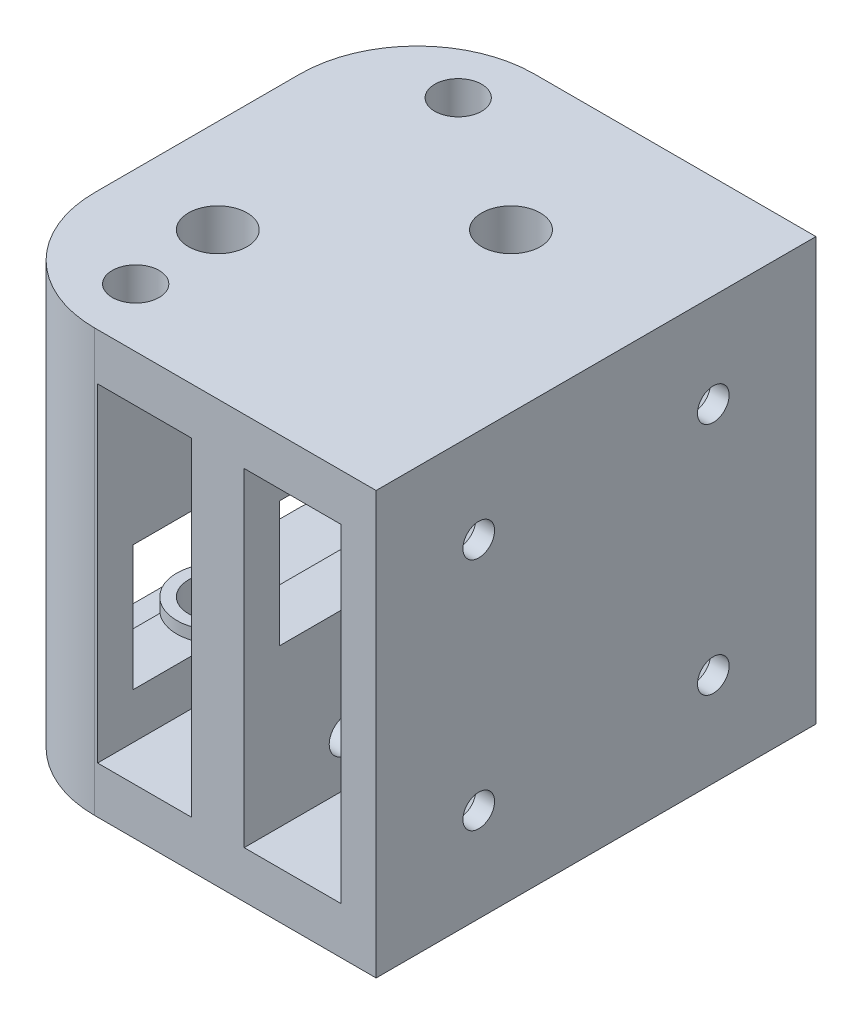
SolidWorks part; units mm, degrees
ref_plane "Front Plane" through (0, 0, 0) normal (0, 0, 1) x (1, 0, 0)
ref_plane "Top Plane" through (0, 0, 0) normal (0, 1, 0) x (1, 0, 0)
ref_plane "Right Plane" through (0, 0, 0) normal (1, 0, 0) x (0, 0, -1)
sketch "Top-Sketch1" plane through (0, 0, 0) normal (0, 1, 0) x (1, 0, 0)
  line L1 (0, 0) -> (34, 0)
  line L2 (0, 0) -> (0, 37.5)
  line L3 (0, 37.5) -> (34, 37.5)
  line L4 (34, 0) -> (34, 37.5)
  circle A0 centre (8.5, 32.5) radius 2
  circle A1 centre (8.5, 5) radius 2
  circle A2 centre (8, 12.5) radius 2.5
  circle A3 centre (20.5, 25) radius 2.5
  dimension "D3" = 5
  dimension "D5" = 4
  dimension "D1" = 13.5
  dimension "D2" = 12.5
  dimension "D4" = 12.5
  dimension "D6" = 8
  dimension "D8" = 12.5
  dimension "D9" = 5
  dimension "D10" = 5
  dimension "D11" = 37.5
  dimension "D12" = 12.5
  dimension "D7" = 25.5
extrude "Boss-Extrude4" add sketch "Top-Sketch1" along normal blind 4
sketch "TopRightRiser" plane through (0, 0, 0) normal (0, -1, 0) x (1, 0, 0)
  line L0 (5.75, -9.819) -> (5.75, 0)
  line L1 (0, 0) -> (34, 0) construction
  line L2 (5.75, 0) -> (10.25, 0)
  line L3 (10.25, 0) -> (10.25, -9.819)
  arc A0 (5.75, -9.819) -> (10.25, -9.819) centre (8, -12.5) ccw
  circle A1 centre (8, -12.5) radius 2.5 construction
  circle A2 centre (8, -12.5) radius 2.5
  point P13 (8, 0)
  dimension "D1" = 7
  dimension "D2" = 4.5
extrude "TopRightRiserBoss-Extrude5" add sketch "TopRightRiser" along normal blind 14.4
sketch "TopLeft" plane through (0, 0, 0) normal (0, -1, 0) x (1, 0, 0)
  line L0 (18.25, -22.319) -> (18.25, 0)
  line L1 (10.25, 0) -> (34, 0) construction
  line L2 (18.25, 0) -> (22.75, 0)
  line L3 (22.75, 0) -> (22.75, -22.319)
  line L4 (10.25, 0) -> (5.75, 0) construction
  circle A0 centre (20.5, -25) radius 2.5
  circle A1 centre (20.5, -25) radius 2.5 construction
  arc A2 (18.25, -22.319) -> (22.75, -22.319) centre (20.5, -25) ccw
  arc A3 (5.75, -9.819) -> (10.25, -9.819) centre (8, -12.5) ccw construction
  point P16 (20.5, 0)
extrude "TopLeftBoss-Extrude6" add sketch "TopLeft" along normal blind 4.9
sketch "MidWall" plane through (0, 0, 0) normal (0, -1, 0) x (-1, 0, 0)
  line L0 (-10.25, 9.819) -> (-10.25, 5.9682) construction
  line L1 (0, 3) -> (-10.25, 3)
  line L2 (0, 3) -> (0, 0)
  line L3 (0, 0) -> (-10.25, 0)
  line L4 (-10.25, 3) -> (-10.25, 0)
  line L5 (0, 37.5) -> (0, 0) construction
  line L6 (-10.25, 0) -> (-5.75, 0) construction
  line L7 (-18.25, 0) -> (-18.25, 22.319) construction
  line L8 (-18.25, 0) -> (-22.75, 0)
  line L9 (-18.25, 0) -> (-18.25, 3)
  line L10 (-18.25, 3) -> (-22.75, 3)
  line L11 (-22.75, 0) -> (-22.75, 3)
  line L12 (-22.75, 22.319) -> (-22.75, 0) construction
  line L13 (-10.25, 0) -> (-18.25, 0) construction
  line L14 (-22.75, 0) -> (-34, 0) construction
  line L15 (-31, 0) -> (-34, 0)
  line L16 (-31, 0) -> (-31, 37.5)
  line L17 (-31, 37.5) -> (-34, 37.5)
  line L18 (-34, 0) -> (-34, 37.5)
  line L19 (-34, 37.5) -> (0, 37.5) construction
  line L20 (-34, 0) -> (-34, 37.5) construction
  dimension "D1" = 3
extrude "MidWallBoss-Extrude7" add sketch "MidWall" along normal blind 28
sketch "Bottom" plane through (0, -28, 0) normal (0, -1, 0) x (1, 0, 0)
  line L0 (0, 0) -> (34, 0) construction
  line L1 (0, 0) -> (34, 0)
  line L2 (0, 0) -> (0, -37.5)
  line L3 (0, -37.5) -> (34, -37.5)
  line L4 (34, 0) -> (34, -37.5)
  line L5 (34, 0) -> (34, -37.5) construction
  line L6 (0, -37.5) -> (0, 0) construction
extrude "BottomBoss-Extrude8" add sketch "Bottom" along normal blind 4
sketch "LowerRight" plane through (0, -28, 0) normal (0, 1, 0) x (1, 0, 0)
  line L0 (5.75, 9.819) -> (5.75, 3)
  line L1 (5.75, 3) -> (10.25, 3)
  line L2 (10.25, 3) -> (10.25, 9.819)
  line L6 (10.25, 9.819) -> (10.25, 3) construction
  line L7 (5.75, 3) -> (5.75, 9.819) construction
  line L8 (10.25, 3) -> (5.75, 3) construction
  circle A0 centre (8, 12.5) radius 2.5
  arc A1 (10.25, 9.819) -> (5.75, 9.819) centre (8, 12.5) ccw
  circle A2 centre (8, 12.5) radius 2.5 construction
  arc A3 (10.25, 9.819) -> (5.75, 9.819) centre (8, 12.5) ccw construction
extrude "LowerRightBoss-Extrude10" add sketch "LowerRight" along normal blind 4.9
sketch "LowerLeft" plane through (0, -28, 0) normal (0, 1, 0) x (1, 0, 0)
  line L1 (18.25, 0) -> (22.75, 0)
  line L5 (0, 0) -> (34, 0) construction
  line L6 (18.25, 22.319) -> (18.25, 0)
  line L7 (22.75, 22.319) -> (22.75, 0)
  circle A0 centre (20.5, 25) radius 2.5
  arc A1 (22.75, 22.319) -> (18.25, 22.319) centre (20.5, 25) ccw
  circle A2 centre (20.5, 25) radius 2.5 construction
  arc A3 (22.75, 22.319) -> (18.25, 22.319) centre (20.5, 25) ccw construction
  point P3 (20.5, 0)
  dimension "D1" = 4.5
extrude "LowerLeftBoss-Extrude9" add sketch "LowerLeft" along normal blind 14.4
fillet "Fillet1" radius 10 3 edges at (0, -14, 0) (0, -30, -37.5) (0, 2, -37.5)
sketch "LinearRailMountingHoles-Sketch10" plane through (34, 0, 0) normal (1, 0, 0) x (0, 0, -1)
  line L0 (0, 4) -> (37.5, 4) construction
  line L1 (37.5, 4) -> (37.5, -32) construction
  line L3 (37.5, -32) -> (0, -32) construction
  line L4 (0, 4) -> (0, -32) construction
  circle A0 centre (8.75, -4) radius 1
  circle A1 centre (8.75, -24) radius 1
  circle A2 centre (28.75, -24) radius 1
  circle A3 centre (28.75, -4) radius 1
  dimension "D7" = 2
  dimension "D1" = 8
  dimension "D2" = 20
  dimension "D3" = 20
  dimension "D4" = 8.75
  dimension "D5" = 8
  dimension "D6" = 8.75
extrude "LinearRailMountingHolesCut-Extrude1" cut sketch "LinearRailMountingHoles-Sketch10" against normal blind 3
sketch "TopRightInset-Sketch1" plane through (0, -14.4, 0) normal (0, -1, 0) x (1, 0, 0)
  line L0 (5.75, -9.819) -> (5.75, -3)
  line L1 (5.75, -3) -> (10.25, -3)
  line L2 (10.25, -3) -> (10.25, -9.819)
  line L3 (5.75, -9.819) -> (5.75, -3) construction
  line L4 (5.75, -3) -> (10.25, -3) construction
  line L5 (10.25, -3) -> (10.25, -9.819) construction
  arc A0 (10.25, -9.819) -> (5.75, -9.819) centre (8, -12.5) ccw
  arc A1 (5.75, -9.819) -> (10.25, -9.819) centre (8, -12.5) ccw construction
extrude "TopRightInset-Cut-Extrude1" cut sketch "TopRightInset-Sketch1" against normal blind 1
sketch "TopLeftInset-Sketch2" plane through (0, -4.9, 0) normal (0, -1, 0) x (1, 0, 0)
  line L0 (18.25, -22.319) -> (18.25, -3)
  line L1 (18.25, -3) -> (22.75, -3)
  line L2 (22.75, -3) -> (22.75, -22.319)
  line L3 (22.75, -3) -> (18.25, -3) construction
  line L4 (22.75, -22.319) -> (22.75, -3) construction
  line L5 (18.25, -22.319) -> (18.25, -3) construction
  arc A0 (22.75, -22.319) -> (18.25, -22.319) centre (20.5, -25) ccw
  arc A1 (18.25, -22.319) -> (22.75, -22.319) centre (20.5, -25) ccw construction
extrude "TopLeftInset-Cut-Extrude2" cut sketch "TopLeftInset-Sketch2" against normal blind 1
sketch "LowerLeftInset-Sketch3" plane through (0, -13.6, 0) normal (0, 1, 0) x (1, 0, 0)
  line L0 (18.25, 22.319) -> (18.25, 3)
  line L1 (18.25, 3) -> (22.75, 3)
  line L2 (22.75, 3) -> (22.75, 22.319)
  line L3 (22.75, 3) -> (18.25, 3) construction
  line L4 (18.25, 22.319) -> (18.25, 3) construction
  line L5 (22.75, 3) -> (22.75, 22.319) construction
  arc A0 (18.25, 22.319) -> (22.75, 22.319) centre (20.5, 25) ccw
  arc A1 (22.75, 22.319) -> (18.25, 22.319) centre (20.5, 25) ccw construction
extrude "LowerLeftInset-Cut-Extrude3" cut sketch "LowerLeftInset-Sketch3" against normal blind 1
sketch "LowerRightInset-Sketch4" plane through (0, -23.1, 0) normal (0, 1, 0) x (1, 0, 0)
  line L0 (5.75, 9.819) -> (5.75, 3)
  line L1 (5.75, 3) -> (10.25, 3)
  line L2 (10.25, 3) -> (10.25, 9.819)
  line L3 (10.25, 3) -> (5.75, 3) construction
  line L4 (5.75, 3) -> (5.75, 9.819) construction
  line L5 (10.25, 9.819) -> (10.25, 3) construction
  arc A0 (5.75, 9.819) -> (10.25, 9.819) centre (8, 12.5) ccw
  arc A1 (10.25, 9.819) -> (5.75, 9.819) centre (8, 12.5) ccw construction
extrude "LowerRightInsetCut-Extrude4" cut sketch "LowerRightInset-Sketch4" against normal blind 1
sketch "PushPinHoleSketch1" plane through (0, -32, 0) normal (0, -1, 0) x (1, 0, 0)
  circle A0 centre (20.5, -25) radius 1
  circle A1 centre (8, -12.5) radius 1
  circle A2 centre (8, -12.5) radius 2.5 construction
  circle A3 centre (20.5, -25) radius 2.5 construction
  dimension "D1" = 2
extrude "PushPinHoleCut-Extrude5" cut sketch "PushPinHoleSketch1" against normal through all
sketch "TopRightMountHoleAccessSketch2" plane through (5.75, 0, 0) normal (-1, 0, 0) x (0, 0, 1)
  circle A0 centre (-8.75, -4) radius 1.5
  dimension "D1" = 3
extrude "TopRightMountHoleAccessCut-Extrude2" cut sketch "TopRightMountHoleAccessSketch2" against normal blind 20 and the other way through all
sketch "BottomRightMountHoleAccessSketch3" plane through (18.25, 0, 0) normal (-1, 0, 0) x (0, 0, 1)
  circle A0 centre (-8.75, -24) radius 1.5
  arc A1 (-9.819, -5.0522) -> (-9.819, -2.9478) centre (-8.75, -4) ccw construction
extrude "BottomRightMountHoleAccessCut-Extrude3" cut sketch "BottomRightMountHoleAccessSketch3" against normal blind 5
sketch "Sketch6" plane through (31, 0, 0) normal (-1, 0, 0) x (0, 0, 1)
  point P0 (-28.75, -4)
  point P3 (-8.75, -4)
  point P6 (-8.75, -24)
  point P9 (-28.75, -24)
hole_wizard "CSK for M2.5 Flat Head Machine Screw1" positions "Sketch6" profile "Sketch7" countersink size "M2.5" standard "ANSI Metric" end condition through all
sketch "Sketch7" plane through (31, -4, -28.75) normal (0, 1, 0) x (0, 0, 1)
  line L0 (0, 0) -> (0, 3)
  line L1 (0, 3) -> (1.35, 3)
  line L2 (1.35, 3) -> (1.35, 1.4)
  line L3 (1.35, 1.4) -> (2.75, 0)
  line L5 (2.75, 0) -> (0, 0)
  line L6 (-1.35, 1.4) -> (-2.75, 0) construction
  line L11 (0, -6.35) -> (0, 107.95) construction
  dimension "Thru Hole Dia." = 2.7
  dimension "Thru Hole Depth" = 3
  dimension "Near C'Sink Dia." = 5.5
  dimension "Near C'Sink Angle" = 90
equation "\"GABDepth\"= \"GABDistanceFromBackToFirstPulley\" + \"GABPulleyDDistanceBetween\" + \"GABDistanceFromPulleyToFront\""
equation "\"GABWidth\"= \"StandardWallThickness\" + \"GABDistanceFromLSideToPulley\" + \"GABPulleyWDistanceBetween\" + \"GABDistanceFromPulleyToRSide\""
equation "\"GABLowerHeight\"= 4mm"
equation "\"GABUpperHeight\"= 4mm"
equation "\"GABMidWallHeight\"= 28mm'Must equal 28 or changes alignment"
equation "\"StandardWallThickness\"= 3mm"
equation "\"GABMidShortRiserHeight\"= \"GABMidWallHeight\" / 2 - \"20TGT2PulleyWidth\"'Equals 5.3"
equation "\"LinearGBMountHolesXDistance\"= 20mm'Spec"
equation "\"GABHeight\"= \"GABLowerHeight\" + \"GABMidWallHeight\" + \"GABUpperHeight\""
equation "\"GBMountingHoleDiameter\"= 2mm"
equation "\"GABMidLongRiserHeight\"= \"GABMidWallHeight\" - \"GABMidShortRiserHeight\" - \"20TGT2PulleyWidth\"'Equals 14"
equation "\"GABLRClampHoleOffsetFromSide\"= 5mm"
equation "\"GABDistanceFromBackToFirstPulley\"= 13.5mm"
equation "\"GABPulleyDDistanceBetween\"= 12.5mm'From the100"
equation "\"GABPulleyWDistanceBetween\"= 14.5mm'From the100"
equation "\"GABDistanceFromPulleyToFront\"= 8mm"
equation "\"GABDistanceFromLSideToPulley\"= 9.5mm + \"StandardWallThickness\""
equation "\"GABDistanceFromPulleyToRSide\"= 7.5mm"
equation "\"GABDistanceToFrontClampHoles\"= 8.5mm"
equation "\"SteelShaft5mmHoleDiameter\"= 5mm"
equation "\"20TGT2PulleyWidth\"= 8.7mm'The STL of the Pulley in the diagram is a bit larger"
equation "\"7mmx1mmSpacerDiameter\"= 7mm"
equation "\"7mmx1mmSpacerHeight\"= 1mm"
equation "\"GABRiserBossOffset\"= 0.4mm'Aligns Pulleys inside edges to be 2.5mm (.5mm apart top to bottom)"
equation "\"D1@Top-Sketch1\" = \"GABDistanceFromBackToFirstPulley\""
equation "\"D2@Top-Sketch1\" = \"GABPulleyDDistanceBetween\""
equation "\"D3@Top-Sketch1\" = \"SteelShaft5mmHoleDiameter\""
equation "\"D4@Top-Sketch1\" = \"GABPulleyDDistanceBetween\""
equation "\"D6@Top-Sketch1\" = \"GABDistanceFromPulleyToFront\""
equation "\"D8@Top-Sketch1\" = \"GABDistanceFromLSideToPulley\""
equation "\"D9@Top-Sketch1\" = \"GABLRClampHoleOffsetFromSide\""
equation "\"D10@Top-Sketch1\" = \"GABLRClampHoleOffsetFromSide\""
equation "\"D11@Top-Sketch1\" = \"GABWidth\""
equation "\"D1@Boss-Extrude4\"=\"GABUpperHeight\""
equation "\"D1@TopRightRiserBoss-Extrude5\" = \"GABMidLongRiserHeight\" + \"GABRiserBossOffset\""
equation "\"D1@TopLeftBoss-Extrude6\" = \"GABMidShortRiserHeight\" - \"GABRiserBossOffset\""
equation "\"D1@MidWall\" = \"StandardWallThickness\""
equation "\"D1@MidWallBoss-Extrude7\" = \"GABMidWallHeight\""
equation "\"D1@BottomBoss-Extrude8\" = \"GABLowerHeight\""
equation "\"D1@LowerLeftBoss-Extrude9\" = \"GABMidLongRiserHeight\" + \"GABRiserBossOffset\""
equation "\"D1@LowerRightBoss-Extrude10\" = \"GABMidShortRiserHeight\" - \"GABRiserBossOffset\""
equation "\"D1@LinearRailMountingHoles-Sketch10\" =  ( \"GABHeight\" - \"LinearGBMountHolesXDistance\" )  / 2"
equation "\"D2@LinearRailMountingHoles-Sketch10\"=\"LinearGBMountHolesYDistance\""
equation "\"D3@LinearRailMountingHoles-Sketch10\" = \"LinearGBMountHolesXDistance\""
equation "\"D4@LinearRailMountingHoles-Sketch10\" =  ( \"GABWidth\" - \"LinearGBMountHolesXDistance\" )  / 2"
equation "\"D7@LinearRailMountingHoles-Sketch10\" = \"GBMountingHoleDiameter\""
equation "\"D1@LinearRailMountingHolesCut-Extrude1\" = \"StandardWallThickness\""
equation "\"D1@TopRightInset-Cut-Extrude1\" = \"7mmx1mmSpacerHeight\""
equation "\"D1@TopLeftInset-Cut-Extrude2\" = \"7mmx1mmSpacerHeight\""
equation "\"D1@LowerRightInsetCut-Extrude4\" = \"7mmx1mmSpacerHeight\""
equation "\"D1@TopRightRiser\"=\"7mmx1mmSpacerDiameter\""
equation "\"D7@Top-Sketch1\"=\"GABDepth\" - \"GABDistanceToFrontClampHoles\""
equation "\"LinearGBMountHolesYDistance\"= 20mm'Spec"
equation "\"D1@PushPinHoleSketch1\" = \"StealPinPushHoleDiameter\""
equation "\"StealPinPushHoleDiameter\"= 2mm"
equation "\"M3HeatInsertHoleDiameter\"= 4mm'Spec"
equation "\"D5@Top-Sketch1\"=\"M3HeatInsertHoleDiameter\""
